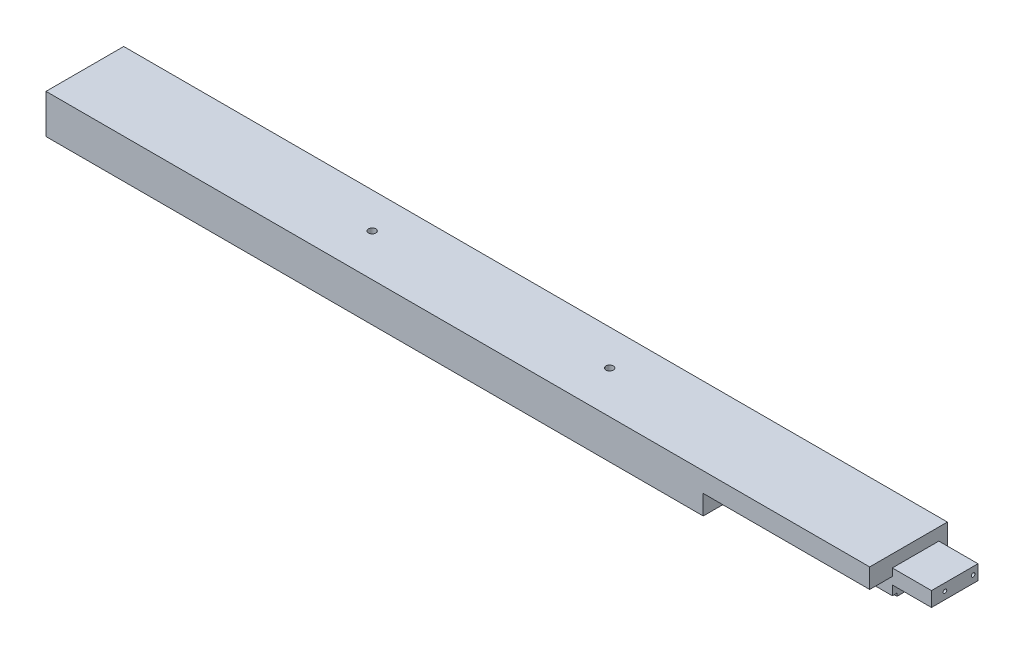
SolidWorks part; units mm, degrees
ref_plane "Front Plane" through (0, 0, 0) normal (0, 0, 1) x (1, 0, 0)
ref_plane "Top Plane" through (0, 0, 0) normal (0, 1, 0) x (1, 0, 0)
ref_plane "Right Plane" through (0, 0, 0) normal (1, 0, 0) x (0, 0, -1)
sketch "Sketch1" plane through (0, 0, 0) normal (0, 1, 0) x (1, 0, 0)
  line L1 (1068.3875, 100.8063) -> (-1068.3875, 100.8062)
  line L2 (1068.3875, 100.8063) -> (1068.3875, -100.8062)
  line L3 (1068.3875, -100.8062) -> (-1068.3875, -100.8063)
  line L4 (-1068.3875, 100.8062) -> (-1068.3875, -100.8063)
  line L5 (1068.3875, 100.8063) -> (-1068.3875, -100.8063) construction
  line L6 (1068.3875, -100.8062) -> (-1068.3875, 100.8062) construction
  point P0 (0, 0)
  dimension "D1" = 201.6125
  dimension "D2" = 2136.775
extrude "Boss-Extrude1" add sketch "Sketch1" along normal blind 101.6
sketch "Sketch2" plane through (0, 101.6, 0) normal (0, 1, 0) x (1, 0, 0)
  line L0 (-1068.3875, 100.8062) -> (-1068.3875, -100.8063) construction
  line L1 (1068.3875, 100.8063) -> (-1068.3875, 100.8062) construction
  circle A0 centre (-331.7875, 8.7313) radius 9.525
  circle A1 centre (284.1625, 8.7313) radius 9.525
  point P8 (0, 0)
  point P9 (0, 0)
  dimension "D1" = 19.05
  dimension "D2" = 615.95
  dimension "D3" = 736.6
  dimension "D4" = 92.075
extrude "Cut-Extrude1" cut sketch "Sketch2" against normal through all
sketch "Sketch3" plane through (1068.3875, 0, 0) normal (1, 0, 0) x (0, 0, -1)
  line L0 (-100.8062, 0) -> (100.8063, 0) construction
  line L1 (-42.0687, 69.85) -> (78.5813, 69.85)
  line L2 (-42.0687, 69.85) -> (-42.0687, 31.75)
  line L3 (-42.0687, 31.75) -> (78.5813, 31.75)
  line L4 (78.5813, 69.85) -> (78.5813, 31.75)
  line L5 (-42.0687, 69.85) -> (78.5813, 31.75) construction
  line L6 (-42.0687, 31.75) -> (78.5813, 69.85) construction
  line L7 (18.2563, 50.8) -> (78.5813, 50.8) construction
  line L8 (100.8063, 101.6) -> (100.8063, 0) construction
  line L9 (-100.8062, 50.8) -> (-42.0687, 50.8)
  line L10 (-100.8062, 101.6) -> (-100.8062, 0) construction
  line L11 (-42.0687, 50.8) -> (-42.0687, 7.3123)
  line L12 (-42.0687, 7.3123) -> (-29.932, 7.3123)
  line L13 (-29.932, 7.3123) -> (-29.932, 0)
  line L14 (-100.8062, 50.8) -> (-100.8062, 0)
  line L15 (-100.8062, 0) -> (-29.932, 0)
  circle A0 centre (65.8813, 50.8) radius 4.7625
  circle A1 centre (-7.1437, 50.8) radius 4.7625
  point P0 (18.2563, 50.8)
  point P15 (-42.0687, 50.8)
  line M6 (-100.8062, 0) -> (100.8063, 0)
  line M9 (-100.8062, 101.6) -> (-100.8062, 0)
  dimension "D4" = 9.525
  dimension "D1" = 38.1
  dimension "D2" = 31.75
  dimension "D3" = 120.65
  dimension "D5" = 34.925
  dimension "D6" = 22.225
  dimension "D7" = 73.025
extrude "Boss-Extrude2" add sketch "Sketch3" along normal blind 101.6 contours L4 L1 L2 L3 A1 A0 region at (1068.3875, 50.8, -17.9007)
extrude "Cut-Extrude2" cut sketch "Sketch3<3>" against normal blind 431.8 contours L13 L12 L11 L2 L9 M9 M6 region at (1068.3875, 24.772, 70.414)
sketch "Sketch3<3>" plane through (1068.3875, 0, 0) normal (1, 0, 0) x (0, 0, -1) same geometry as "Sketch3"
sketch "Sketch5" plane through (0, 0, 0) normal (0, -1, 0) x (1, 0, 0)
  line L1 (1068.3875, -100.8063) -> (-1068.3875, -100.8062) construction
  circle A0 centre (1009.3067, 7.1437) radius 11.1125
  circle A1 centre (1009.3067, -65.8813) radius 11.1125
  point P4 (0, 0)
  dimension "D1" = 22.225
  dimension "D2" = 73.025
  dimension "D3" = 34.925
extrude "Cut-Extrude3" cut sketch "Sketch5" against normal blind 69.85
